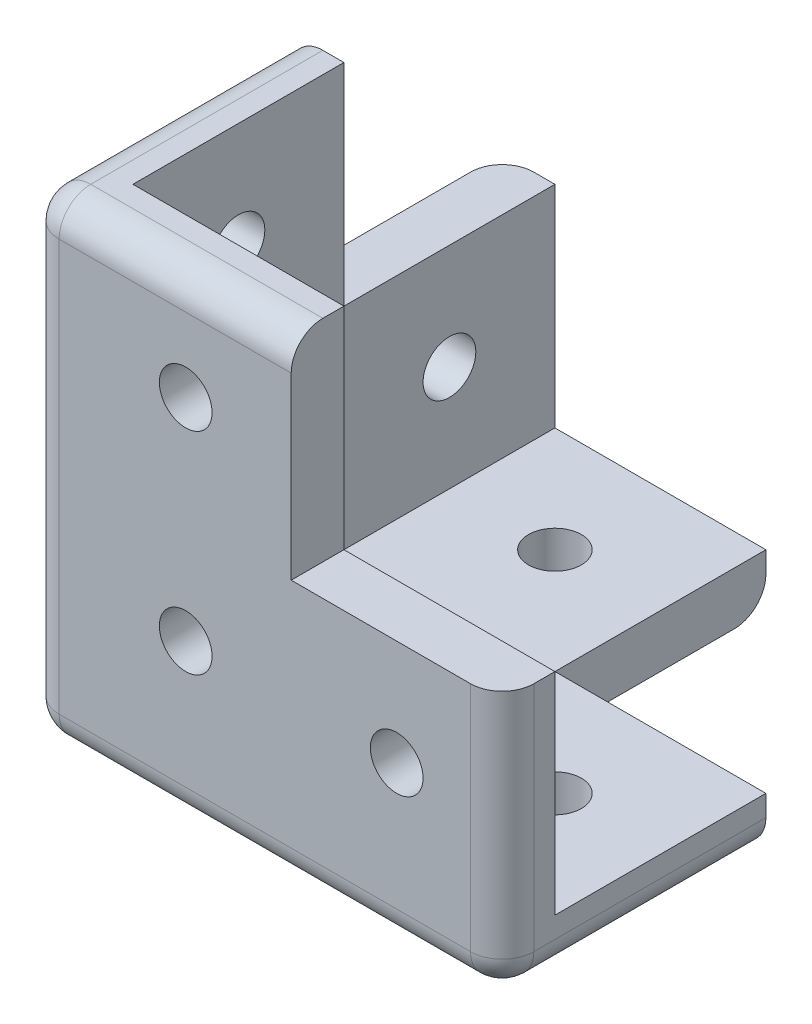
SolidWorks part; units mm, degrees
ref_plane "정면" through (0, 0, 0) normal (0, 0, 1) x (1, 0, 0)
ref_plane "윗면" through (0, 0, 0) normal (0, 1, 0) x (1, 0, 0)
ref_plane "우측면" through (0, 0, 0) normal (1, 0, 0) x (0, 0, -1)
sketch "스케치1" plane through (0, 0, 0) normal (0, 1, 0) x (1, 0, 0)
  line L1 (0, 0) -> (40, 0)
  line L2 (0, 0) -> (0, 40)
  line L3 (0, 40) -> (40, 40)
  line L4 (40, 0) -> (40, 40)
  line L5 (40, 40) -> (20, 40)
  line L6 (40, 40) -> (40, 20)
  line L7 (40, 20) -> (20, 20)
  line L8 (20, 40) -> (20, 20)
  line L9 (20, 20) -> (0, 20)
  line L10 (20, 20) -> (20, 0)
  line L11 (20, 0) -> (0, 0)
  line L12 (0, 20) -> (0, 0)
  dimension "D1" = 40
  dimension "D2" = 40
  dimension "D3" = 20
  dimension "D4" = 20
extrude "보스-돌출1" add sketch "스케치1" along normal blind 20 contours L9 L8 L3 L2 | L7 L10 L1 L4 region at (30, 0, -10) region at (10, 0, -30)
extrude "보스-돌출2" add sketch "스케치1<3>" along normal blind 40 contours L10 L9 L2 L1 region at (10, 0, -10)
sketch "스케치1<3>" plane through (0, 0, 0) normal (0, 1, 0) x (1, 0, 0) same geometry as "스케치1"
sketch "스케치2" plane through (0, 0, 0) normal (0, 0, 1) x (1, 0, 0)
  line L6 (0, 0) -> (40, 0)
  line L7 (40, 0) -> (40, 20)
  line L8 (40, 20) -> (20, 20)
  line L9 (20, 20) -> (20, 40)
  line L10 (20, 40) -> (0, 40)
  line L11 (0, 40) -> (0, 0)
  line L12 (0, 0) -> (40, 0)
  line L13 (40, 0) -> (40, 20)
  line L14 (40, 20) -> (20, 20)
  line L15 (20, 20) -> (20, 40)
  line L16 (20, 40) -> (0, 40)
  line L17 (0, 40) -> (0, 0)
  dimension "D1" = 0
extrude "보스-돌출3" add sketch "스케치2" along normal blind 5 separate body
sketch "스케치3" plane through (0, 0, 0) normal (-1, 0, 0) x (0, 0, 1)
  line L4 (0, 40) -> (0, 0)
  line L5 (0, 0) -> (5, 0)
  line L6 (5, 0) -> (5, 40)
  line L7 (5, 40) -> (0, 40)
  line L8 (0, 40) -> (0, 0)
  line L9 (0, 0) -> (5, 0)
  line L10 (5, 0) -> (5, 40)
  line L11 (5, 40) -> (0, 40)
  line L14 (-40, 0) -> (0, 0)
  line L15 (0, 0) -> (0, 40)
  line L16 (0, 40) -> (-20, 40)
  line L17 (-20, 40) -> (-20, 20)
  line L18 (-20, 20) -> (-40, 20)
  line L19 (-40, 20) -> (-40, 0)
  line L20 (-40, 0) -> (0, 0)
  line L21 (0, 0) -> (0, 40)
  line L22 (0, 40) -> (-20, 40)
  line L23 (-20, 40) -> (-20, 20)
  line L24 (-20, 20) -> (-40, 20)
  line L25 (-40, 20) -> (-40, 0)
  line M11 (0, 40) -> (0, 0)
  line M12 (0, 0) -> (5, 0)
  line M13 (5, 0) -> (5, 40)
  line M14 (5, 40) -> (0, 40)
  dimension "D1" = 0
  dimension "D2" = 0
extrude "보스-돌출4" add sketch "스케치3" along normal blind 5 separate body contours L24 L25 L20 L22 L23 M11 | M14 M11 M12 M13 region at (0, 20, 2.5) region at (0, 16.6667, -16.6667)
sketch "스케치5" plane through (0, 0, 0) normal (0, -1, 0) x (1, 0, 0)
  line L4 (0, 0) -> (40, 0)
  line L5 (40, 0) -> (40, 5)
  line L6 (40, 5) -> (0, 5)
  line L7 (0, 5) -> (0, 0)
  line L8 (0, 0) -> (40, 0)
  line L9 (40, 0) -> (40, 5)
  line L10 (40, 5) -> (0, 5)
  line L11 (0, 5) -> (0, 0)
  line L12 (0, -40) -> (0, 5)
  line L13 (0, 5) -> (-5, 5)
  line L14 (20, -40) -> (20, -20)
  line L15 (20, -20) -> (40, -20)
  line L16 (40, -20) -> (40, 0)
  line L17 (40, 0) -> (0, 0)
  line L18 (0, 0) -> (0, -40)
  line L19 (0, -40) -> (20, -40)
  line L20 (20, -40) -> (20, -20)
  line L21 (20, -20) -> (40, -20)
  line L22 (40, -20) -> (40, 0)
  line L23 (40, 0) -> (0, 0)
  line L24 (0, 0) -> (0, -40)
  line L25 (0, -40) -> (20, -40)
  line L26 (-5, 5) -> (-5, -40)
  line L27 (-5, -40) -> (0, -40)
  line L28 (0, -40) -> (0, 5)
  line L29 (0, 5) -> (-5, 5)
  line L30 (-5, 5) -> (-5, -40)
  line L31 (-5, -40) -> (0, -40)
  line M15 (0, 0) -> (40, 0)
  line M16 (40, 0) -> (40, 5)
  line M17 (40, 5) -> (0, 5)
  line M18 (0, 5) -> (0, 0)
  dimension "D1" = 0
  dimension "D2" = 0
  dimension "D3" = 0
extrude "보스-돌출5" add sketch "스케치5" along normal blind 5 contours M18 M15 M16 M17 | L24 L25 L20 L21 L22 M15 | L30 L31 L24 L29 M18 region at (20, 0, 2.5) region at (-2.5, 0, -17.5) region at (16.6667, 0, -16.6667)
sketch "스케치6" plane through (0, 40, 0) normal (0, 1, 0) x (1, 0, 0)
  line L4 (20, -5) -> (20, 20) construction
  line L5 (20, 20) -> (-5, 20) construction
  line L6 (-5, 20) -> (-5, -5) construction
  line L7 (-5, -5) -> (20, -5) construction
  line L8 (40, 20) -> (20, 20) construction
  line L9 (20, 20) -> (20, -5) construction
  line L10 (20, -5) -> (40, -5) construction
  line L11 (40, -5) -> (40, 20) construction
  line L16 (-5, 20) -> (20, 20) construction
  line L17 (20, 20) -> (20, 40) construction
  line L18 (20, 40) -> (-5, 40) construction
  line L19 (-5, 40) -> (-5, 20) construction
  line L20 (20, -5) -> (20, 20)
  line L21 (20, 20) -> (-5, 20)
  line L22 (-5, 20) -> (-5, -5)
  line L23 (-5, -5) -> (20, -5)
  line L24 (40, 20) -> (20, 20)
  line L25 (20, 20) -> (20, -5)
  line L26 (20, -5) -> (40, -5)
  line L27 (40, -5) -> (40, 20)
  line L28 (-5, 20) -> (20, 20)
  line L29 (20, 20) -> (20, 40)
  line L30 (20, 40) -> (-5, 40)
  line L31 (-5, 40) -> (-5, 20)
  line L32 (20, 0) -> (35, 0)
  line L33 (35, 0) -> (35, 15)
  line L34 (35, 15) -> (20, 15)
  line L35 (0, 20) -> (0, 0)
  line L36 (0, 0) -> (20, 0)
  line L37 (15, 20) -> (15, 35)
  line L38 (15, 35) -> (0, 35)
  line L39 (0, 35) -> (0, 20)
  line L40 (35, 0) -> (40, 0)
  line L41 (0, 35) -> (0, 40)
  line M5 (20, -5) -> (20, 20)
  line M6 (20, 20) -> (-5, 20)
  dimension "D1" = 5
extrude "컷-돌출1" cut sketch "스케치6" against normal blind 40 contours L35 L36 L25 L28 M5 M6 | L38 L39 L28 L37 | L41 L38 L37 L29 L30 M6 | L33 L34 L25 L32 | L33 L40 L27 L24 L34 M5 region at (10, 40, -10) region at (27.5, 40, -7.5) region at (20.2828, 40, -17.5) region at (17.5, 40, -20.2828) region at (7.5, 40, -27.5)
sketch "스케치7" plane through (0, 0, 0) normal (0, 1, 0) x (1, 0, 0)
  line L0 (10, 40) -> (10, 0) construction
  line L1 (20, 40) -> (0, 40) construction
  line L2 (0, 0) -> (20, 0) construction
  line L3 (40, 10) -> (0, 10) construction
  line L4 (40, 0) -> (40, 20) construction
  line L5 (0, 20) -> (0, 0) construction
  line L6 (20, 30) -> (0, 30) construction
  line L7 (20, 20) -> (20, 40) construction
  line L8 (0, 40) -> (0, 20) construction
  line L9 (30, 20) -> (30, 0) construction
  line L10 (40, 20) -> (20, 20) construction
  line L11 (20, 0) -> (40, 0) construction
  circle A0 centre (10, 30) radius 2.5
  circle A1 centre (30, 10) radius 2.5
  circle A2 centre (10, 10) radius 2.5
  dimension "D1" = 5
extrude "컷-돌출2" cut sketch "스케치7" against normal blind 5
sketch "스케치9" plane through (0, 0, 0) normal (0, 0, -1) x (-1, 0, 0)
  line L0 (-10, 40) -> (-10, 0) construction
  line L1 (0, 40) -> (-20, 40) construction
  line L2 (0, 0) -> (-40, 0) construction
  line L3 (-40, 10) -> (0, 10) construction
  line L4 (-40, 0) -> (-40, 20) construction
  line L5 (0, 0) -> (0, 20) construction
  line L6 (-30, 20) -> (-30, 0) construction
  line L7 (-20, 20) -> (-40, 20) construction
  line L8 (-40, 0) -> (-20, 0) construction
  line L9 (-20, 30) -> (0, 30) construction
  line L10 (-20, 40) -> (-20, 20) construction
  line L11 (0, 40) -> (0, 20) construction
  circle A0 centre (-10, 30) radius 2.5
  circle A1 centre (-30, 10) radius 2.5
  circle A2 centre (-10, 10) radius 2.5
  dimension "D1" = 5
extrude "컷-돌출3" cut sketch "스케치9" against normal blind 5
sketch "스케치10" plane through (0, 0, 0) normal (1, 0, 0) x (0, 0, -1)
  line L0 (10, 40) -> (10, 0) construction
  line L1 (20, 40) -> (0, 40) construction
  line L2 (40, 0) -> (0, 0) construction
  line L3 (40, 10) -> (0, 10) construction
  line L4 (40, 0) -> (40, 20) construction
  line L5 (0, 0) -> (0, 40) construction
  line L6 (20, 30) -> (0, 30) construction
  line L7 (20, 40) -> (20, 20) construction
  line L8 (30, 20) -> (30, 0) construction
  line L9 (40, 20) -> (20, 20) construction
  circle A0 centre (10, 30) radius 2.5
  circle A1 centre (30, 10) radius 2.5
  circle A2 centre (10, 10) radius 2.5
  dimension "D1" = 5
extrude "컷-돌출4" cut sketch "스케치10" against normal blind 5
fillet "필렛1" radius 3 9 edges at (-5, 7.5, -40) (7.5, -5, -40) (40, -5, -7.5) (40, 7.5, 5) (17.5, -5, 5) (-5, -5, -17.5) (-5, 17.5, 5) (-5, 40, -7.5) (7.5, 40, 5)
